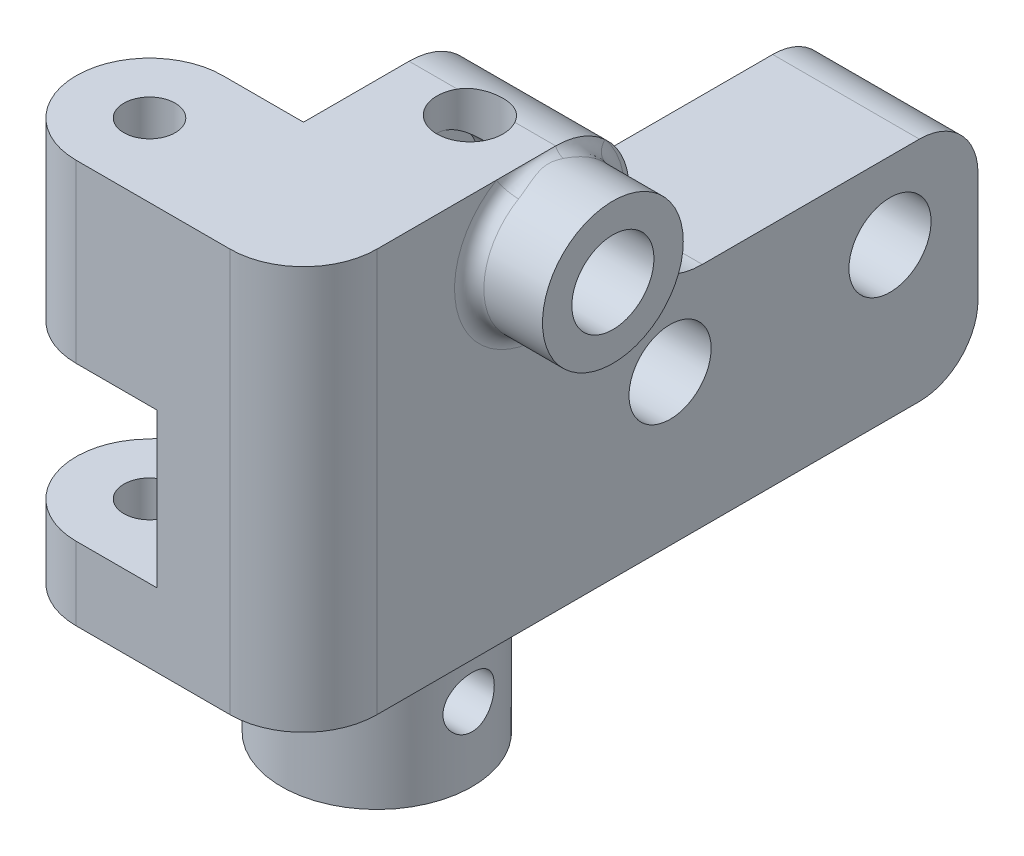
SolidWorks part; units mm, degrees
ref_plane "Front Plane" through (0, 0, 0) normal (0, 0, 1) x (1, 0, 0)
ref_plane "Top Plane" through (0, 0, 0) normal (0, 1, 0) x (1, 0, 0)
ref_plane "Right Plane" through (0, 0, 0) normal (1, 0, 0) x (0, 0, -1)
sketch "Sketch1" plane through (0, 0, 0) normal (0, 1, 0) x (1, 0, 0)
  line L0 (0, 0) -> (5.5, 0) construction
  line L1 (0, 5) -> (5.5, 5)
  line L2 (0, -5) -> (5.5, -5)
  line L3 (5.5, 5) -> (5.5, 31)
  line L4 (5.5, -5) -> (15.5, -5)
  line L6 (5.5, 31) -> (15.5, 31)
  line L7 (15.5, -5) -> (15.5, 31)
  line L8 (5.5, 20) -> (15.5, 20) construction
  arc A0 (0, 5) -> (0, -5) centre (0, 0) ccw
  circle A2 centre (0, 0) radius 1.75
  circle A3 centre (5.5, 10) radius 39 construction
  dimension "D1" = 5
  dimension "D2" = 3.5
  dimension "D5" = 78
  dimension "D3" = 5.5
  dimension "D4" = 10
  dimension "D6" = 10
  dimension "D7" = 10
  dimension "D8" = 11
extrude "Boss-Extrude1" add sketch "Sketch1" along normal blind 5
sketch "Sketch2" plane through (0, 5, 0) normal (0, 1, 0) x (1, 0, 0)
  line L1 (5.5, 31) -> (15.5, 31)
  line L2 (5.5, 31) -> (5.5, -5)
  line L3 (5.5, -5) -> (15.5, -5)
  line L4 (15.5, 31) -> (15.5, -5)
extrude "Boss-Extrude2" add sketch "Sketch2" along normal blind 10.5
sketch "Sketch3" plane through (0, 15.5, 0) normal (0, 1, 0) x (1, 0, 0)
  line L0 (5.5, 5) -> (15.5, 5)
  line L3 (5.5, -5) -> (5.5, 5)
  line L4 (5.5, 31) -> (5.5, -5)
  line L5 (5.5, -5) -> (15.5, -5)
  line L6 (15.5, -5) -> (15.5, 31)
  line L7 (15.5, 31) -> (5.5, 31)
  line L9 (5.5, -5) -> (15.5, -5)
  line L10 (15.5, -5) -> (15.5, 5)
  line L12 (5.5, 5) -> (0, 5)
  line L13 (0, -5) -> (5.5, -5)
  line L15 (5.5, 5) -> (0, 5)
  line L16 (0, -5) -> (5.5, -5)
  circle A0 centre (0, 0) radius 1.75 construction
  arc A1 (0, 5) -> (0, -5) centre (0, 0) ccw
  arc A2 (0, 5) -> (0, -5) centre (0, 0) ccw
  circle A3 centre (0, 0) radius 1.75
  dimension "D1" = 0
  dimension "D2" = 0
extrude "Boss-Extrude3" add sketch "Sketch3" along normal blind 5
fillet "Fillet1" radius 5 1 edges at (15.5, 10.25, 5)
sketch "Sketch4" plane through (15.5, 0, 0) normal (1, 0, 0) x (0, 0, -1)
  line L0 (1.75, 20.5) -> (-1.75, 20.5) construction
  line L1 (1.75, 20.5) -> (-1.75, 20.5)
  line L2 (0, 20.5) -> (0, 10.25) construction
  line L3 (0, 20.5) -> (0, 0) construction
  line L4 (0, 10.25) -> (20, 10.25) construction
  circle A0 centre (20, 10.25) radius 2.8
  dimension "D2" = 5.6
  dimension "D1" = 20
extrude "Cut-Extrude1" cut sketch "Sketch4" against normal through all contours A0 region at (15.5, 10.25, -20)
sketch "Sketch5" plane through (0, 0, 0) normal (0, -1, 0) x (1, 0, 0)
  line L0 (5.5, -31) -> (5.5, -5) construction
  circle A0 centre (5.5, -10) radius 6.5
  circle A1 centre (0, 0) radius 1.75 construction
  circle A2 centre (0, 0) radius 1.75 construction
  circle A3 centre (5.5, -10) radius 2.5
  dimension "D2" = 13
  dimension "D3" = 5
  dimension "D1" = 10
extrude "Boss-Extrude4" add sketch "Sketch5" along normal blind 11
sketch "Sketch6" plane through (0, 0, 0) normal (0, 1, 0) x (1, 0, 0)
  line L3 (5.5, 12.5) -> (5.5, 16.5)
  line L4 (1.3467, 5) -> (5.5, 5)
  line L5 (5.5, 5) -> (5.5, 7.5)
  line L6 (5.5, 12.5) -> (5.5, 16.5)
  line L7 (1.3467, 5) -> (5.5, 5)
  line L8 (5.5, 5) -> (5.5, 7.5)
  arc A2 (5.5, 16.5) -> (1.3467, 5) centre (5.5, 10) ccw
  arc A3 (5.5, 12.5) -> (5.5, 7.5) centre (5.5, 10) ccw
  arc A4 (5.5, 16.5) -> (1.3467, 5) centre (5.5, 10) ccw
  arc A5 (5.5, 12.5) -> (5.5, 7.5) centre (5.5, 10) ccw
  dimension "D1" = 0
extrude "Boss-Extrude5" add sketch "Sketch6" along normal up to surface (5 mm away) up to face at (1.5, 5, 0)
sketch "Sketch7" plane through (0, 0, 0) normal (1, 0, 0) x (0, 0, -1)
  line L0 (10, -11) -> (10, -6) construction
  line L1 (3.5, -11) -> (16.5, -11) construction
  circle A0 centre (10, -6) radius 1.75
  dimension "D1" = 3.5
  dimension "D2" = 5
extrude "Cut-Extrude2" cut sketch "Sketch7" against normal through all both and the other way through all
sketch "Sketch8" plane through (15.5, 0, 0) normal (1, 0, 0) x (0, 0, -1)
  circle A0 centre (13.5, 10.25) radius 1.6
  circle A1 centre (26.5, 10.25) radius 1.6
  circle A2 centre (20, 10.25) radius 2.8 construction
  circle A3 centre (20, 10.25) radius 2.8 construction
  dimension "D2" = 3.2
  dimension "D3" = 3.2
  dimension "D1" = 6.5
  dimension "D4" = 6.5
extrude "Cut-Extrude3" [suppressed] cut sketch "Sketch8" against normal blind 8
fillet "Fillet2" radius 5 2 edges at (10.5, 0, -31) (10.5, 15.5, -31)
chamfer "Chamfer1" [suppressed] distance 1 angle 45
fillet "Fillet3" radius 5 1 edges at (10.5, 15.5, -5)
sketch "Sketch9" plane through (5.5, 0, 0) normal (-1, 0, 0) x (0, 0, 1)
  line L0 (-26, 15.5) -> (-10, 15.5) construction
  line L1 (-17.2, 15.5) -> (-5, 15.5)
  line L2 (-17.2, 15.5) -> (-17.2, 27.5)
  line L3 (-17.2, 27.5) -> (-5, 27.5)
  line L4 (-5, 15.5) -> (-5, 27.5)
  line L5 (-5, 20.5) -> (-5, 15.5) construction
  circle A0 centre (-20, 10.25) radius 2.8 construction
  dimension "D1" = 12
extrude "Boss-Extrude6" add sketch "Sketch9" against normal up to surface (10 mm away) up to face at (15.5, 10.25, -22.8)
fillet "Fillet4" [suppressed] radius 4
fillet "Fillet5" [suppressed] radius 2
sketch "Sketch10" [suppressed] plane through (0, 27.5, 0) normal (0, 1, 0) x (1, 0, 0)
  line L0 (10.5, 11.1) -> (10.5, 7) construction
  line L1 (5.5, 7) -> (15.5, 7) construction
  line L2 (10.5, 11.1) -> (5.5, 11.1) construction
  line L3 (5.5, 7) -> (5.5, 15.2) construction
  line L5 (9.5, 13.35) -> (11.5, 13.35) construction
  line L6 (9.5, 13.35) -> (9.5, 8.85) construction
  line L7 (9.5, 8.85) -> (11.5, 8.85) construction
  line L8 (11.5, 13.35) -> (11.5, 8.85) construction
  line L9 (9.5, 13.35) -> (11.5, 8.85) construction
  line L10 (9.5, 8.85) -> (11.5, 13.35) construction
  circle A1 centre (10.5, 11.1) radius 2
  dimension "D1" = 4.5
  dimension "D3" = 4
  dimension "D2" = 2
extrude "Cut-Extrude4" [suppressed] cut sketch "Sketch10" against normal blind 10
sketch "Sketch11" plane through (15.5, 0, 0) normal (1, 0, 0) x (0, 0, -1)
  line L0 (11.1, 22.5) -> (11.1, 27.5) construction
  line L1 (17.2, 27.5) -> (5, 27.5) construction
  circle A0 centre (11.1, 22.5) radius 2.8
  dimension "D1" = 5.6
  dimension "D2" = 5
extrude "Cut-Extrude5" cut sketch "Sketch11" against normal blind 7
sketch "Sketch12" plane through (15.5, 0, 0) normal (1, 0, 0) x (0, 0, -1)
  circle A0 centre (11.1, 22.5) radius 2.8 construction
  circle A1 centre (11.1, 22.5) radius 2.8
  circle A2 centre (11.1, 22.5) radius 4.8
  dimension "D1" = 2
extrude "Boss-Extrude7" add sketch "Sketch12" along normal blind 5
chamfer "Chamfer2" distance 3 angle 45 1 edges at (5.5, -11, -12.5)
chamfer "Chamfer3" distance 3 angle 45 1 edges at (5.5, 0, -10)
fillet "Fillet6" radius 2 1 edges at (3, 5, -10)
sketch "Sketch13" plane through (5.5, 0, 0) normal (-1, 0, 0) x (0, 0, 1)
  line L0 (-26, 15.5) -> (-17.2, 15.5) construction
  line L1 (-26, 0) -> (-37, 0)
  line L2 (-26, 0) -> (-26, 15.5)
  line L3 (-26, 15.5) -> (-37, 15.5)
  line L4 (-41, 4) -> (-41, 11.5)
  circle A0 centre (-35, 10.25) radius 2.8
  circle A1 centre (-20, 10.25) radius 2.8 construction
  circle A2 centre (-20, 10.25) radius 2.8 construction
  arc A3 (-37, 0) -> (-41, 4) centre (-37, 4) cw
  arc A4 (-37, 15.5) -> (-41, 11.5) centre (-37, 11.5) ccw
  dimension "D1" = 5.6
  dimension "D3" = 4
  dimension "D2" = 15
  dimension "D4" = 6
extrude "Boss-Extrude8" add sketch "Sketch13" against normal up to surface (10 mm away) up to face at (15.5, 10.25, -22.8)
sketch "Sketch14" plane through (0, 20.5, 0) normal (0, 1, 0) x (1, 0, 0)
  line L4 (0, -5) -> (10.5, -5)
  line L5 (15.5, 0) -> (15.5, 5)
  line L6 (15.5, 5) -> (5.5, 5)
  line L7 (5.5, 5) -> (0, 5)
  line L8 (0, -5) -> (10.5, -5)
  line L9 (15.5, 0) -> (15.5, 5)
  line L10 (15.5, 5) -> (5.5, 5)
  line L11 (5.5, 5) -> (0, 5)
  circle A0 centre (0, 0) radius 1.75 construction
  circle A1 centre (0, 0) radius 1.75
  arc A2 (10.5, -5) -> (15.5, 0) centre (10.5, 0) ccw
  arc A3 (0, 5) -> (0, -5) centre (0, 0) ccw
  arc A4 (10.5, -5) -> (15.5, 0) centre (10.5, 0) ccw
  arc A5 (0, 5) -> (0, -5) centre (0, 0) ccw
  dimension "D1" = 0
extrude "Boss-Extrude9" add sketch "Sketch14" along normal up to surface (7 mm away) up to face at (10.5, 27.5, -11.1)
fillet "Fillet7" radius 10 1 edges at (1.3467, 2.5, -5)
fillet "Fillet8" radius 5 2 edges at (10.5, 27.5, -17.2) (10.5, 15.5, -17.2)
sketch "Sketch15" plane through (0, 27.5, 0) normal (0, 1, 0) x (1, 0, 0)
  line L0 (8.5, 8.3) -> (8.5, 13.9) construction
  line L1 (8.5, 8.3) -> (8.5, 13.9) construction
  line L2 (10.75, 11.1) -> (8.5, 11.1) construction
  circle A0 centre (10.75, 11.1) radius 2.25
  dimension "D1" = 4.5
extrude "Cut-Extrude6" cut sketch "Sketch15" against normal blind 10
fillet "Fillet9" radius 1 1 edges at (15.5, 22.5, -6.3)
